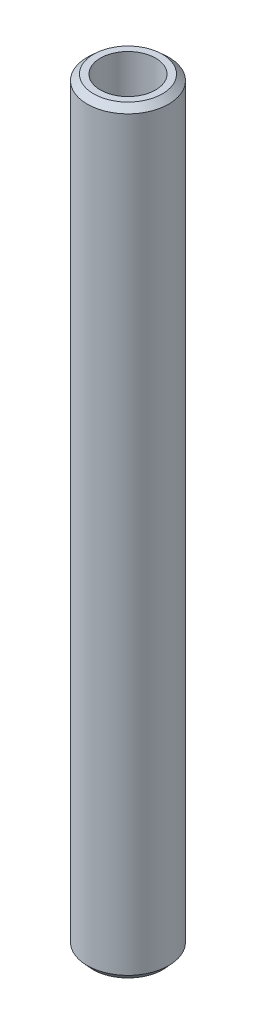
SolidWorks part; units mm, degrees
ref_plane "Front Plane" through (0, 0, 0) normal (0, 0, 1) x (1, 0, 0)
ref_plane "Top Plane" through (0, 0, 0) normal (0, 1, 0) x (1, 0, 0)
ref_plane "Right Plane" through (0, 0, 0) normal (1, 0, 0) x (0, 0, -1)
sketch "Sketch1" plane through (0, 0, 0) normal (0, 1, 0) x (1, 0, 0)
  circle A0 centre (0, 0) radius 15
  dimension "SHAFT_OD" = 30
extrude "Boss-Extrude1" add sketch "Sketch1" along normal blind 279.5379
sketch "Sketch2" plane through (0, 0, 0) normal (0, 1, 0) x (1, 0, 0)
  circle A0 centre (0, 0) radius 10.1851
  dimension "BORE_D" = 20.3701
extrude "Cut-Extrude1" cut sketch "Sketch2" along normal through all
chamfer "Chamfer1" distance 2.1121 angle 47.864 2 edges at (0, 279.5379, 15) (0, 0, 15) first distance on face at (0, 279.5379, 15) first distance on face at (0, 0, 10.1851)
